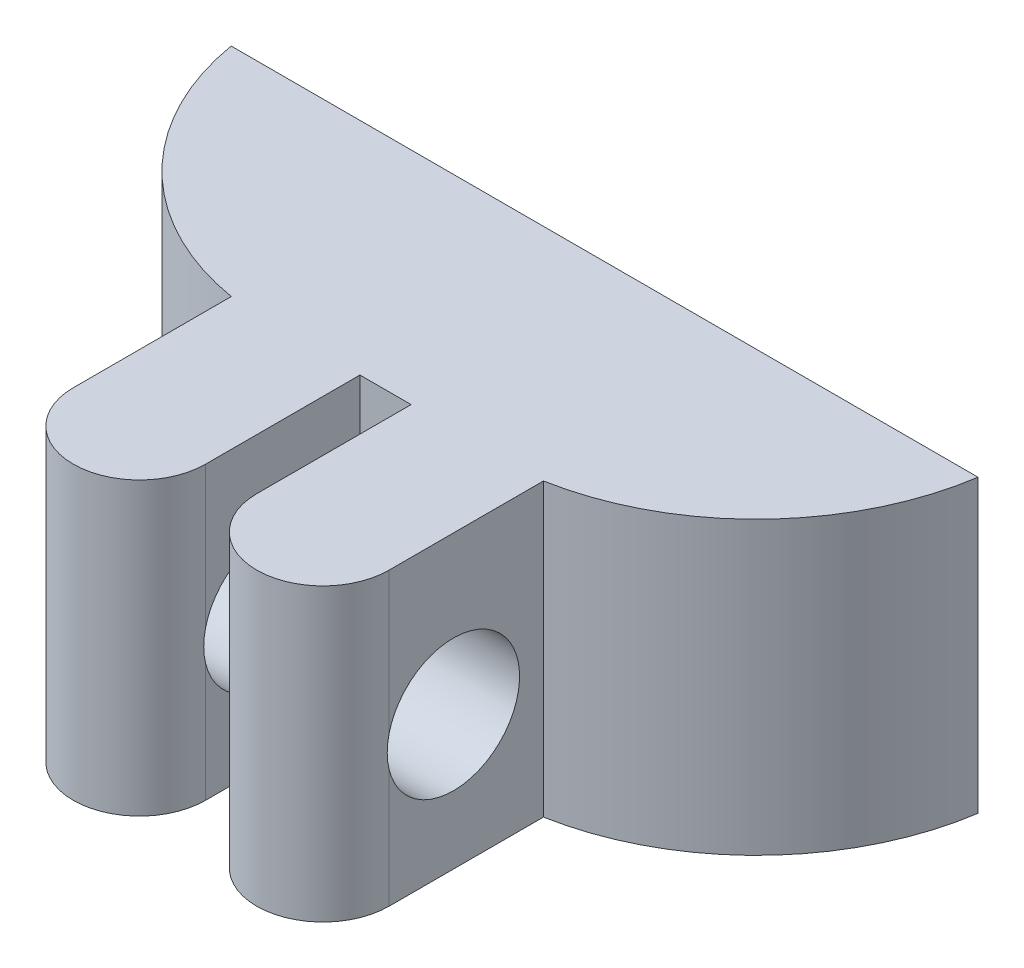
SolidWorks part; units mm, degrees
ref_plane "Front Plane" through (0, 0, 0) normal (0, 0, 1) x (1, 0, 0)
ref_plane "Top Plane" through (0, 0, 0) normal (0, 1, 0) x (1, 0, 0)
ref_plane "Right Plane" through (0, 0, 0) normal (1, 0, 0) x (0, 0, -1)
sketch "Sketch1" plane through (0, 0, 0) normal (0, 0, 1) x (1, 0, 0)
  line L1 (0, 0) -> (-17, 0)
  line L2 (0, 0) -> (0, -15)
  line L3 (0, -15) -> (-17, -15)
  line L4 (-17, 0) -> (-17, -15)
  dimension "D1" = 15
  dimension "D2" = 17
extrude "Boss-Extrude1" add sketch "Sketch1" along normal blind 5
sketch "Sketch2" plane through (0, 0, 5) normal (0, 0, 1) x (1, 0, 0)
  line L0 (0, 0) -> (-17, 0) construction
  line L1 (-7.92, 0) -> (-4.92, 0)
  line L2 (-7.92, 0) -> (-7.92, -15)
  line L3 (-7.92, -15) -> (-4.92, -15)
  line L4 (-4.92, 0) -> (-4.92, -15)
  line L5 (-17, -15) -> (0, -15) construction
  line L7 (-8.5, 0) -> (-8.5, -15) construction
  line L8 (-12.08, -0.0236) -> (-9.08, -0.0236)
  line L9 (-12.08, -0.0236) -> (-12.08, -15)
  line L10 (-12.08, -15) -> (-9.08, -15)
  line L11 (-9.08, -0.0236) -> (-9.08, -15)
  dimension "D1" = 4.92
  dimension "D2" = 3
  dimension "D3" = 4.92
extrude "Boss-Extrude2" add sketch "Sketch2" along normal blind 5
sketch "Sketch4" plane through (-9.08, 0, 0) normal (1, 0, 0) x (0, 0, -1)
  circle A0 centre (-7.0414, -7.7625) radius 1.5
  dimension "D1" = 3
extrude "Cut-Extrude2" cut sketch "Sketch4" against normal through all both and the other way through all
fillet "Fillet1" radius 6 2 edges at (-17, -7.5, 5) (0, -7.5, 5)
fillet "Fillet3" 2 edges at (-12.08, -7.5118, 10) (-9.08, -7.5118, 10) type full round first side face at (-12.08, -6.2625, 7.0414) second side face at (-9.08, -9.2625, 7.0414) middle face at (-10.58, -7.5118, 10)
fillet "Fillet4" 2 edges at (-7.92, -7.5, 10) (-4.92, -7.5, 10) type full round first side face at (-7.92, -6.2625, 7.0414) second side face at (-4.92, -9.2625, 7.0414) middle face at (-6.42, -7.5, 10)
sketch "Sketch5" plane through (0, 0, 0) normal (0, 0, 1) x (1, 0, 0)
  line L0 (-17, 0) -> (-17, -15) construction
  line L1 (0, 0) -> (-17, 0)
  line L2 (0, 0) -> (0, -4.2)
  line L3 (0, -4.2) -> (-17, -4.2)
  line L4 (-17, 0) -> (-17, -4.2)
  line L6 (-0.0682, -15) -> (-17, -15)
  line L7 (-0.0682, -15) -> (-0.0682, -10.8)
  line L8 (-0.0682, -10.8) -> (-17, -10.8)
  line L9 (-17, -15) -> (-17, -10.8)
  dimension "D1" = 4.2
  dimension "D2" = 4.2
extrude "Cut-Extrude3" cut sketch "Sketch5" along normal blind 14
